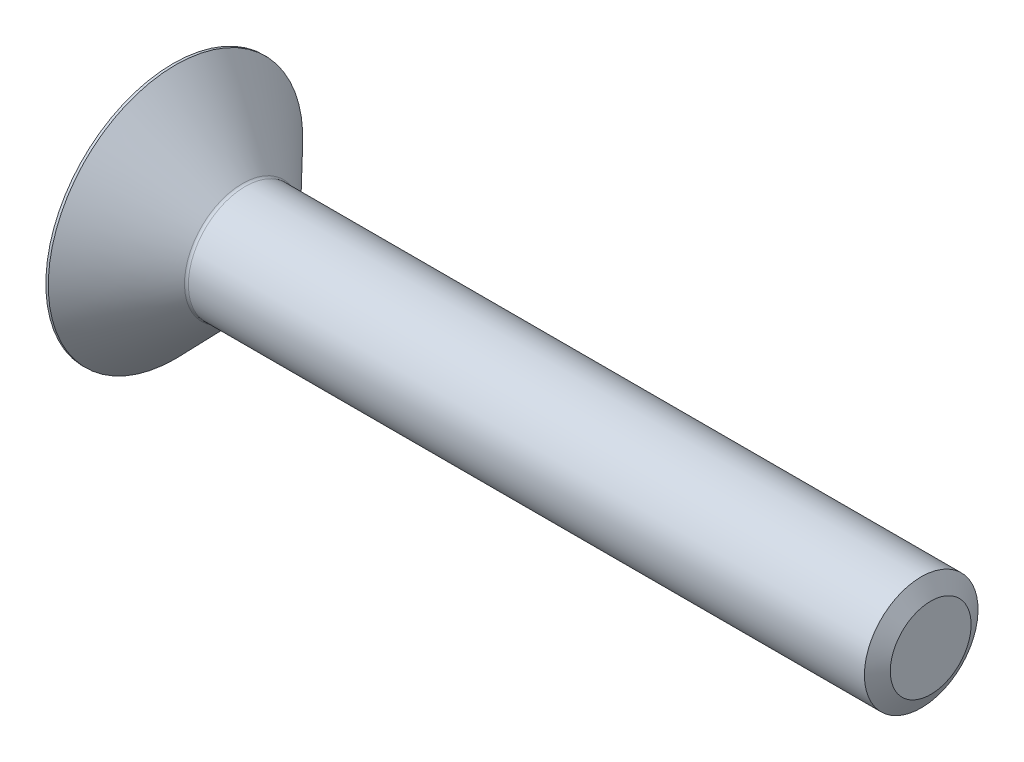
SolidWorks part; units mm, degrees
ref_plane "前视基准面" through (0, 0, 0) normal (0, 0, 1) x (1, 0, 0)
ref_plane "上视基准面" through (0, 0, 0) normal (0, 1, 0) x (1, 0, 0)
ref_plane "右视基准面" through (0, 0, 0) normal (1, 0, 0) x (0, 0, -1)
sketch "尺寸草图" plane through (0, 0, 0) normal (0, 0, 1) x (1, 0, 0)
  line L0 (0, 0) -> (20, 0) construction
  line L1 (20, 0) -> (20, 1.5) construction
  line L2 (20, 1.5) -> (19.5, 1.5) construction
  line L3 (19.5, 1.5) -> (2, 1.5) construction
  line L4 (0, 3.36) -> (1.86, 3.36) construction
  line L5 (1.86, 3.36) -> (1.96, 3.36) construction
  point P3 (20, 1.65)
  point P7 (0, 3.36)
  point P8 (0, 1.5)
  point P9 (0, 2.3)
  point P13 (0, 1)
  point P15 (1.1, 3.36)
  point P16 (1.71, 3.36)
  dimension "l" = 20
  dimension "d" = 3
  dimension "P" = 0.5
  dimension "b" = 18
  dimension "da" = 3.3
  dimension "dk" = 6.72
  dimension "ds" = 3
  dimension "e" = 2.3
  dimension "k" = 1.86
  dimension "r" = 0.1
  dimension "s" = 2
  dimension "t" = 1.1
  dimension "w" = 0.25
sketch "草图1" plane through (0, 0, 0) normal (0, 0, 1) x (1, 0, 0)
  line L0 (0, 1.5) -> (-18.0976, 1.5)
  line L1 (-18.1695, 1.5305) -> (-19.9362, 3.36)
  line L2 (-19.9362, 3.36) -> (-20, 3.36)
  line L3 (-20, 3.36) -> (-20, 0)
  line L4 (-20, 0) -> (0, 0)
  line L5 (0, 0) -> (0, 1.5)
  line L6 (0, 0) -> (-20, 0) construction
  arc A0 (-18.0976, 1.5) -> (-18.1695, 1.5305) centre (-18.0976, 1.6) cw
  point P9 (-18.14, 1.5)
  dimension "r" = 0.1
  dimension "k" = 1.86
  dimension "dk" = 6.72
  dimension "l" = 20
  dimension "D5" = 46
  dimension "d" = 3
revolve "旋转1" add sketch "草图1" angle 360 about L6
cosmetic thread "装饰螺纹线1" parameters "b"=18, "D2"=2.4
sketch "草图2" plane through (-20, 0, 0) normal (-1, 0, 0) x (0, 0, 1)
  line L0 (0, 0) -> (0, 1.5) construction
  line L1 (0, 1.1547) -> (-1, 0.5774)
  line L2 (-1, 0.5774) -> (-1, -0.5774)
  line L3 (-1, -0.5774) -> (0, -1.1547)
  line L4 (0, -1.1547) -> (1, -0.5774)
  line L5 (1, -0.5774) -> (1, 0.5774)
  line L6 (1, 0.5774) -> (0, 1.1547)
  circle A0 centre (0, 0) radius 1 construction
  point P1 (0, 1.1453)
  dimension "s" = 2
  dimension "e" = 2.3
extrude "切除-拉伸1" cut sketch "草图2" against normal blind 1.86
sketch "草图6" plane through (0, 0, 0) normal (0, 0, 1) x (1, 0, 0)
  line L0 (-18.9, 1.1547) -> (-18.2333, 0)
  line L1 (-18.2333, 0) -> (-17.84, 0)
  line L2 (-17.84, 0) -> (-17.84, 1.1547)
  line L3 (-17.84, 1.1547) -> (-18.9, 1.1547)
  line L4 (-20, 0) -> (-18.14, 0) construction
  line L5 (-20, 0) -> (-22.3, 0) construction
  dimension "D1" = 60
  dimension "t" = 1.1
  dimension "t1" = 1.86
  dimension "e-s" = 0.3
  dimension "e" = 2.3
revolve "旋转2" add sketch "草图6" angle 360 about L4
sketch "草图7" plane through (0, 0, 0) normal (0, 0, 1) x (1, 0, 0)
  line L0 (-20, 1.1547) -> (-20, 0)
  line L1 (-20, 0) -> (-19.7, 0)
  line L2 (-19.7, 0) -> (-20, 1.1547)
  line L3 (-20, 0) -> (-19.7, 0) construction
  dimension "e-s*1.1" = 0.3
revolve "切除-旋转2" cut sketch "草图7" angle 360 about L3
sketch "草图4" plane through (0, 0, 0) normal (0, 0, 1) x (1, 0, 0)
  line L0 (-0.25, 1.5) -> (0, 1.067)
  line L1 (0, -1.5) -> (0, 1.5) construction
  line L2 (0, 1.067) -> (0.25, 1.5)
  line L3 (0.25, 1.5) -> (-0.25, 1.5)
  line L4 (-0.25, 0) -> (0.25, 0) construction
  dimension "d" = 3
  dimension "p" = 0.5
revolve "切除-旋转1" cut sketch "草图4" angle 360 about L4
ref_axis "基准轴1" through (-21.1715, 0, 0) along (1, 0, 0)
pattern_linear "阵列(线性)2" [suppressed] count 36 spacing 0.5 along (-1, 0, 0) of bodies 104
